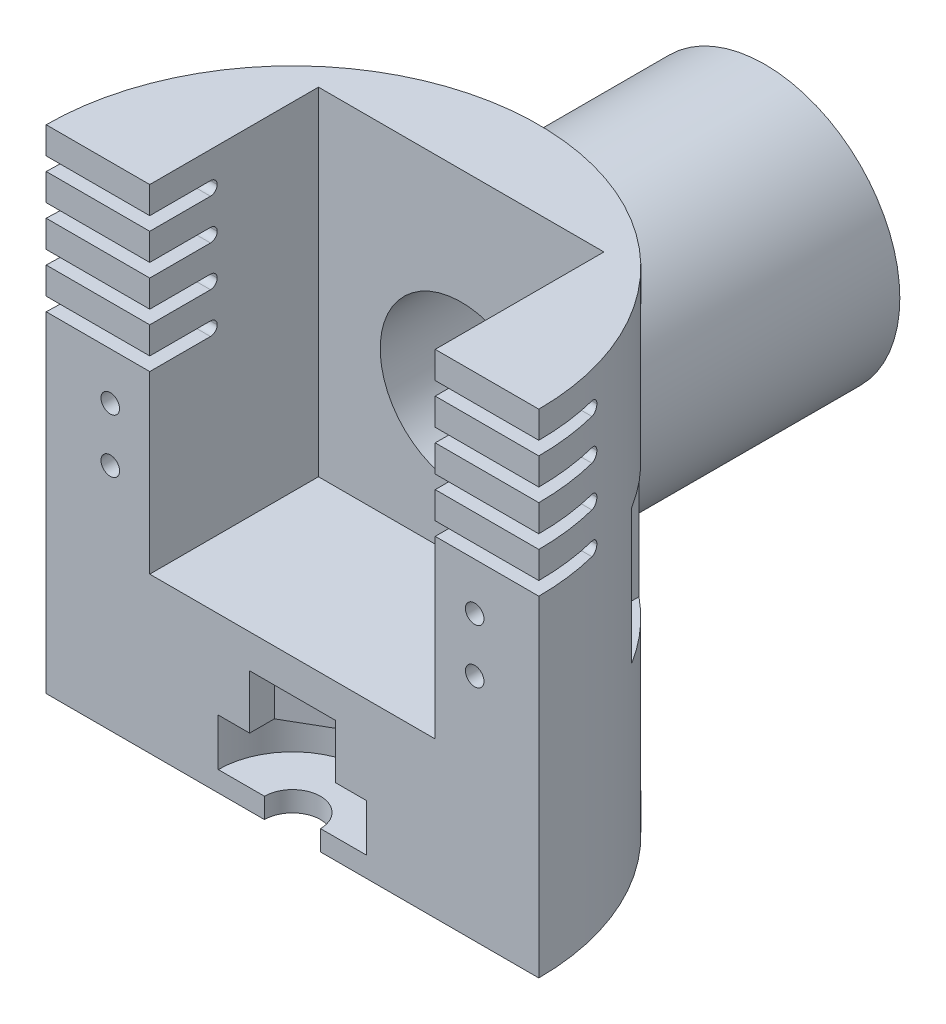
SolidWorks part; units mm, degrees
ref_plane "Front Plane" through (0, 0, 0) normal (0, 0, 1) x (1, 0, 0)
ref_plane "Top Plane" through (0, 0, 0) normal (0, 1, 0) x (1, 0, 0)
ref_plane "Right Plane" through (0, 0, 0) normal (1, 0, 0) x (0, 0, -1)
sketch "Sketch1" plane through (0, 0, 0) normal (0, 1, 0) x (1, 0, 0)
  circle A0 centre (0, 0) radius 36.5
  dimension "D1" = 73
extrude "Boss-Extrude1" add sketch "Sketch1" along normal blind 3
sketch "Sketch2" plane through (0, 3, 0) normal (0, 1, 0) x (1, 0, 0)
  line L0 (-11, 0) -> (-11, -34.803)
  line L1 (11, 0) -> (11, -34.803)
  arc A0 (11, -34.803) -> (-11, -34.803) centre (0, 0) ccw
  arc A1 (11, 0) -> (-11, 0) centre (0, 0) ccw
  dimension "D1" = 73
  dimension "D2" = 11
extrude "Boss-Extrude2" add sketch "Sketch2" along normal blind 7
sketch "Sketch3" plane through (0, 3, 0) normal (0, 1, 0) x (1, 0, 0)
  circle A0 centre (0, 0) radius 4.15
  dimension "D1" = 8.3
extrude "Cut-Extrude1" cut sketch "Sketch3" against normal up to next
sketch "Sketch4" plane through (0, 10, 0) normal (0, 1, 0) x (1, 0, 0)
  line L1 (-6.35, -3.6662) -> (-6.35, -35.9434)
  line L3 (6.35, -3.6662) -> (6.35, 3.6662)
  line L4 (6.35, 3.6662) -> (0, 7.3323)
  line L5 (0, 7.3323) -> (-6.35, 3.6662)
  line L6 (-6.35, 3.6662) -> (-6.35, -3.6662)
  line L8 (6.35, -3.6662) -> (6.35, -35.9434)
  line L10 (-3.175, -5.4993) -> (-0.7775, -6.8834) [skipped]
  line L11 (3.175, -5.4993) -> (6.35, -3.6662) [skipped]
  arc A0 (6.35, -35.9434) -> (-6.35, -35.9434) centre (0, 0) ccw
  arc A1 (6.35, 0) -> (-6.35, 0) centre (0, 0) ccw construction
  arc A2 (6.35, -35.9434) -> (-6.35, -35.9434) centre (0, 0) ccw
  arc M3 (-11, 0) -> (11, 0) centre (0, 0) cw
  line M4 (11, 0) -> (11, -34.803)
  arc M5 (11, -34.803) -> (-11, -34.803) centre (0, 0) ccw
  line M6 (-11, -34.803) -> (-11, 0)
  dimension "D1" = 73
  dimension "D2" = 6.35
extrude "Boss-Extrude3" add sketch "Sketch4" along normal blind 8 contours M6 M3 M4 M5 | L8 A0 L1 L6 L5 L4 L3 M4 M3 M6 region at (-6.8684, 10, 19.8048) region at (0, 10, -35.4796)
sketch "Sketch5" plane through (0, 18, 0) normal (0, 1, 0) x (1, 0, 0)
  line L5 (0, 0) -> (24, 21.15) construction
  circle A0 centre (0, 0) radius 36.5
  dimension "D1" = 73
extrude "Boss-Extrude4" add sketch "Sketch5" along normal blind 5
sketch "Sketch6" plane through (0, 23, 0) normal (0, 1, 0) x (1, 0, 0)
  line L1 (-21.15, -25) -> (21.15, -25)
  line L2 (-21.15, -25) -> (-21.15, 25)
  line L3 (-21.15, 25) -> (21.15, 25)
  line L4 (21.15, -25) -> (21.15, 25)
  line L5 (-21.15, -25) -> (21.15, 25) construction
  line L6 (-21.15, 25) -> (21.15, -25) construction
  circle A0 centre (0, 0) radius 36.5
  dimension "D1" = 73
  dimension "D2" = 42.3
  dimension "D3" = 50
extrude "Boss-Extrude5" add sketch "Sketch6" along normal blind 50
ref_plane "Plane1" through (0, 0, 36.5) normal (0, 0, -1) x (-1, 0, 0)
sketch "Sketch7" plane through (0, 0, 36.5) normal (0, 0, -1) x (-1, 0, 0)
  line L0 (-36.5, 0) -> (36.5, 0) construction
  line L1 (-15.1333, 2.0001) -> (14.8667, 2.0001)
  line L3 (-15.0444, 21.9999) -> (14.9556, 21.9999)
  line L6 (-5.6045, 15.7698) -> (5.6045, 8.2302) construction
  line L7 (0, 12) -> (5.6933, 15.7697) construction
  arc A0 (-15.0444, 21.9999) -> (-15.1333, 2.0001) centre (-15.0444, 11.9998) ccw
  arc A1 (14.8667, 2.0001) -> (14.9556, 21.9999) centre (14.9556, 11.9998) ccw
  point P0 (0, 12)
  dimension "D1" = 12
  dimension "D2" = 20
  dimension "D3" = 30
  dimension "D4" = 30
extrude "Cut-Extrude3" cut sketch "Sketch7" along normal blind 12
ref_plane "Plane2" through (0, 0, -70) normal (0, 0, 1) x (1, 0, 0)
sketch "Sketch10" plane through (0, 0, -70) normal (0, 0, 1) x (1, 0, 0)
  line L0 (-36.5, 0) -> (36.5, 0) construction
  circle A0 centre (0, 44) radius 20
  dimension "D1" = 40
  dimension "D2" = 44
extrude "Boss-Extrude6" add sketch "Sketch10" along normal up to next
sketch "Sketch8" plane through (0, 73, 0) normal (0, 1, 0) x (1, 0, 0)
  line L1 (-36.5, 0) -> (36.5, 0)
  line L2 (-36.5, 0) -> (-36.5, -36.5)
  line L3 (-36.5, -36.5) -> (36.5, -36.5)
  line L4 (36.5, 0) -> (36.5, -36.5)
  circle A0 centre (0, 0) radius 36.5 construction
  dimension "D1" = 73
  dimension "D2" = 36.5
extrude "Cut-Extrude4" cut sketch "Sketch8" against normal through all
sketch "Sketch9" plane through (0, 0, -25) normal (0, 0, 1) x (1, 0, 0)
  line L0 (21.15, 73) -> (21.15, 23) construction
  line L1 (21.15, 23) -> (-21.15, 23) construction
  circle A0 centre (0, 44) radius 4
  dimension "D1" = 21.15
  dimension "D2" = 8
  dimension "D3" = 21
extrude "Cut-Extrude5" cut sketch "Sketch9" against normal up to next
sketch "Sketch11" plane through (0, 0, -70) normal (0, 0, -1) x (-1, 0, 0)
  circle A0 centre (0, 44) radius 11
  dimension "D1" = 22
extrude "Cut-Extrude6" cut sketch "Sketch11" against normal blind 7
sketch "Sketch12" plane through (0, 0, -25) normal (0, 0, 1) x (1, 0, 0)
  circle A0 centre (0, 44) radius 12
  dimension "D1" = 24
extrude "Cut-Extrude7" cut sketch "Sketch12" against normal blind 35
ref_plane "Plane3" through (0, 0, -7.6) normal (0, 0, 1) x (1, 0, 0)
sketch "Sketch13" plane through (0, 0, -7.6) normal (0, 0, 1) x (1, 0, 0)
  line L0 (0, -38.5) -> (0, 38.5) construction
  line L1 (-23, 48) -> (-31, 48)
  line L2 (-23, 48) -> (-23, 28)
  line L3 (-23, 28) -> (-31, 28)
  line L4 (-31, 48) -> (-31, 28)
  line L5 (31, 48) -> (23, 48)
  line L6 (31, 48) -> (31, 28)
  line L7 (31, 28) -> (23, 28)
  line L8 (23, 48) -> (23, 28)
  line L9 (36.5, 73) -> (-36.5, 73) construction
  dimension "D1" = 8
  dimension "D2" = 8
  dimension "D3" = 23
  dimension "D4" = 23
  dimension "D5" = 25
  dimension "D6" = 25
  dimension "D7" = 20
  dimension "D8" = 20
extrude "Cut-Extrude9" cut sketch "Sketch13" against normal up to next
sketch "Sketch14" plane through (0, 0, -7.6) normal (0, 0, -1) x (-1, 0, 0)
  line L0 (23, 48) -> (31, 48) construction
  line L1 (-31, 48) -> (-23, 48) construction
  line L2 (23, 48) -> (23, 28) construction
  line L3 (-23, 28) -> (-23, 48) construction
  line L4 (-23, 48) -> (-23, 28) construction
  circle A0 centre (27, 42) radius 1.375
  circle A1 centre (27, 34) radius 1.375
  circle A2 centre (-27, 42) radius 1.375
  circle A3 centre (-27, 34) radius 1.375
  dimension "D1" = 2.75
  dimension "D2" = 2.75
  dimension "D3" = 2.75
  dimension "D4" = 2.75
  dimension "D5" = 6
  dimension "D6" = 6
  dimension "D7" = 8
  dimension "D8" = 8
  dimension "D9" = 4
  dimension "D10" = 4
  dimension "D11" = 4
  dimension "D12" = 4
extrude "Cut-Extrude10" cut sketch "Sketch14" against normal up to next
sketch "Sketch16" plane through (0, 0, -7.6) normal (0, 0, -1) x (-1, 0, 0)
  circle A0 centre (-27, 42) radius 2.65
  circle A1 centre (-27, 34) radius 2.65
  circle A2 centre (27, 42) radius 2.65
  circle A3 centre (27, 34) radius 2.65
  dimension "D1" = 5.3
  dimension "D2" = 5.3
  dimension "D3" = 5.3
  dimension "D4" = 5.3
extrude "Cut-Extrude14" cut sketch "Sketch16" against normal blind 2.6
ref_plane "Plane4" through (36.5, 0, 0) normal (1, 0, 0) x (0, 0, -1)
sketch "Sketch17" plane through (36.5, 0, 0) normal (1, 0, 0) x (0, 0, -1)
  line L0 (0, 0) -> (0, 73) construction
  line L1 (0, 69) -> (10, 69)
  line L2 (0, 69) -> (0, 67)
  line L3 (0, 67) -> (10, 67)
  line L4 (10, 69) -> (10, 67)
  line L6 (0, 63) -> (10, 63)
  line L7 (0, 63) -> (0, 61)
  line L8 (0, 61) -> (10, 61)
  line L9 (10, 63) -> (10, 61)
  line L10 (0, 57) -> (10, 57)
  line L11 (0, 57) -> (0, 55)
  line L12 (0, 55) -> (10, 55)
  line L13 (10, 57) -> (10, 55)
  line L14 (0, 51) -> (10, 51)
  line L15 (0, 51) -> (0, 49)
  line L16 (0, 49) -> (10, 49)
  line L17 (10, 51) -> (10, 49)
  dimension "D1" = 10
  dimension "D2" = 2
  dimension "D3" = 2
  dimension "D4" = 2
  dimension "D5" = 2
  dimension "D6" = 4
  dimension "D7" = 4
  dimension "D8" = 4
  dimension "D9" = 4
  dimension "D10" = 10
  dimension "D11" = 10
  dimension "D12" = 10
extrude "Cut-Extrude15" cut sketch "Sketch17" against normal through all
fillet "Fillet1" radius 1 16 edges at (-28.1267, 49, -10) (-28.1267, 55, -10) (-28.1267, 61, -10) (-28.1267, 67, -10) (28.1267, 67, -10) (28.1267, 61, -10) (28.1267, 55, -10) (28.1267, 49, -10) (28.1267, 51, -10) (28.1267, 57, -10) (28.1267, 63, -10) (28.1267, 69, -10) (-28.1267, 51, -10) (-28.1267, 57, -10) (-28.1267, 63, -10) (-28.1267, 69, -10)
